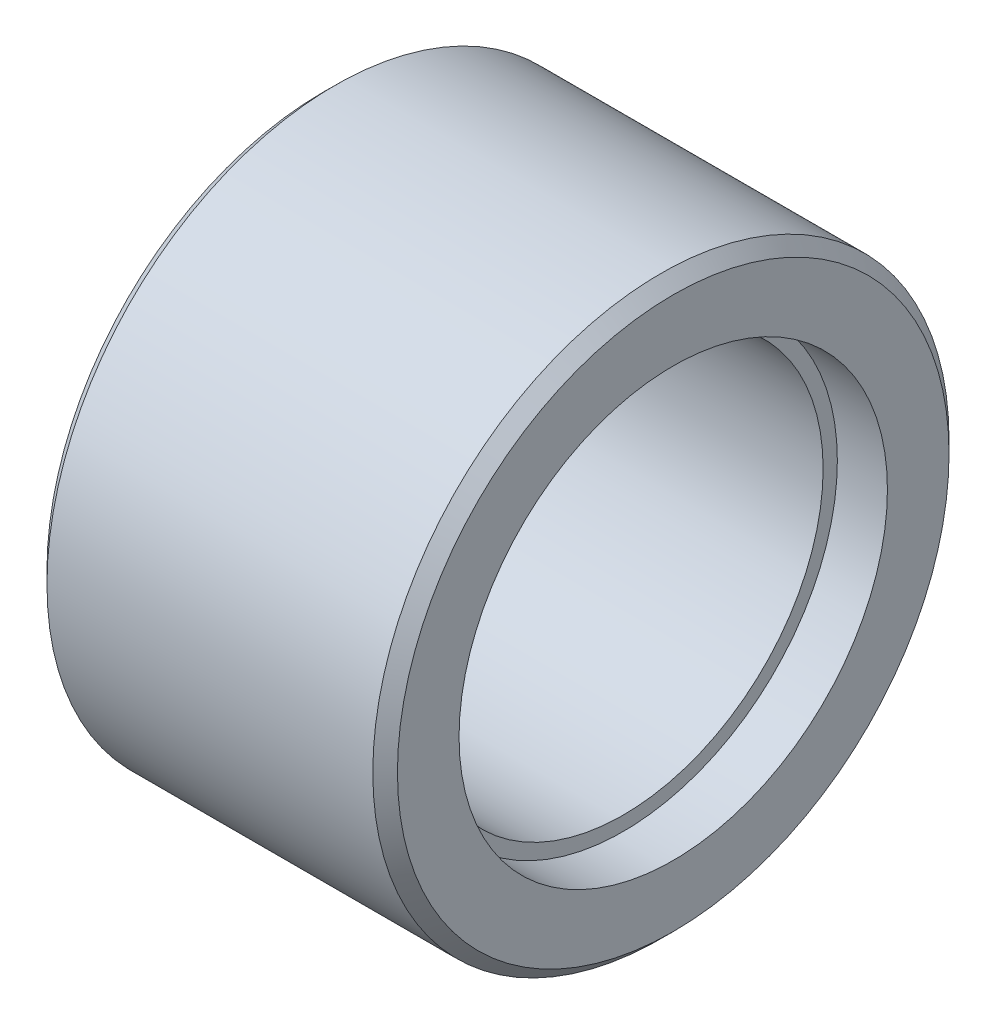
SolidWorks part; units mm, degrees
material "Rubber"
ref_plane "Front Plane" through (0, 0, 0) normal (0, 0, 1) x (1, 0, 0)
ref_plane "Top Plane" through (0, 0, 0) normal (0, 1, 0) x (1, 0, 0)
ref_plane "Right Plane" through (0, 0, 0) normal (1, 0, 0) x (0, 0, -1)
sketch "Sketch1" plane through (0, 0, 0) normal (0, 0, 1) x (1, 0, 0)
  line L0 (0, 0) -> (-92.7637, 0) construction
  line L1 (-75.8997, 8.6931) -> (-73.8677, 8.6931)
  line L2 (-73.8677, 8.6931) -> (-73.8677, 8.1153)
  line L3 (-73.8677, 8.1153) -> (-63.7077, 8.1153)
  line L4 (-63.7077, 8.1153) -> (-63.7077, 8.6931)
  line L5 (-63.7077, 8.6931) -> (-61.6757, 8.6931)
  line L6 (-61.6757, 8.6931) -> (-61.6757, 11.1931)
  line L7 (-62.1757, 11.6931) -> (-75.3997, 11.6931)
  line L8 (-75.8997, 11.1931) -> (-75.8997, 8.6931)
  line L9 (-75.3997, 11.6931) -> (-75.8997, 11.1931)
  line L10 (-61.6757, 11.1931) -> (-62.1757, 11.6931)
  point P10 (-61.6757, 11.6931)
  point P11 (-75.8997, 11.6931)
  dimension "D1" = 16.2306
  dimension "D2" = 17.3863
  dimension "D3" = 17.3863
  dimension "D4" = 10.16
  dimension "D5" = 2.032
  dimension "D6" = 14.224
  dimension "D7" = 3
  dimension "D11" = 0.5
  dimension "D12" = 0.5
revolve "Revolve1" add sketch "Sketch1" angle 360 about L0
